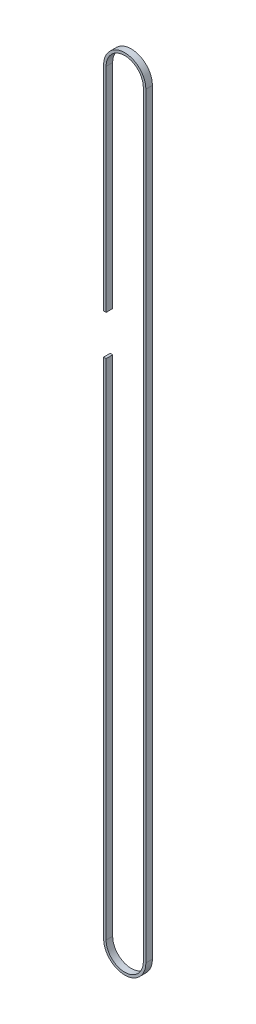
SolidWorks part; units mm, degrees
material "Cast Alloy Steel"
ref_plane "Front Plane" through (0, 0, 0) normal (0, 0, 1) x (1, 0, 0)
ref_plane "Top Plane" through (0, 0, 0) normal (0, 1, 0) x (1, 0, 0)
ref_plane "Right Plane" through (0, 0, 0) normal (1, 0, 0) x (0, 0, -1)
sketch "Sketch1" plane through (0, 0, 0) normal (0, 0, 1) x (1, 0, 0)
  line L0 (-25.1587, 901.7) -> (-25.1587, 647.7)
  line L1 (25.1587, 0) -> (25.1587, 901.7)
  line L2 (22.1615, 0) -> (22.1615, 901.7)
  line L3 (-22.1615, 901.7) -> (-22.1615, 647.7)
  line L4 (-25.1587, 647.7) -> (-22.1615, 647.7)
  line L5 (-22.1615, 600.075) -> (-25.1587, 600.075)
  line L6 (-25.1587, 600.075) -> (-25.1587, 0)
  line L7 (-25.1587, 901.7) -> (-25.1587, 0) construction
  line L8 (-22.1615, 600.075) -> (-22.1615, 0)
  line L9 (-22.1615, 901.7) -> (-22.1615, 0) construction
  circle A0 centre (0, 0) radius 25.1587 construction
  circle A1 centre (0, 901.7) radius 25.1587 construction
  arc A2 (-25.1587, 901.7) -> (25.1587, 901.7) centre (0, 901.7) cw
  arc A3 (-25.1587, 0) -> (25.1587, 0) centre (0, 0) ccw
  arc A4 (-22.1615, 901.7) -> (22.1615, 901.7) centre (0, 901.7) cw
  arc A5 (-22.1615, 0) -> (22.1615, 0) centre (0, 0) ccw
  dimension "D2" = 50.3174
  dimension "D1" = 901.7
  dimension "D4" = 47.625
  dimension "D5" = 254
  dimension "D3" = 2.9972
extrude "Boss-Extrude1" add sketch "Sketch1" along normal mid plane 7.7978
